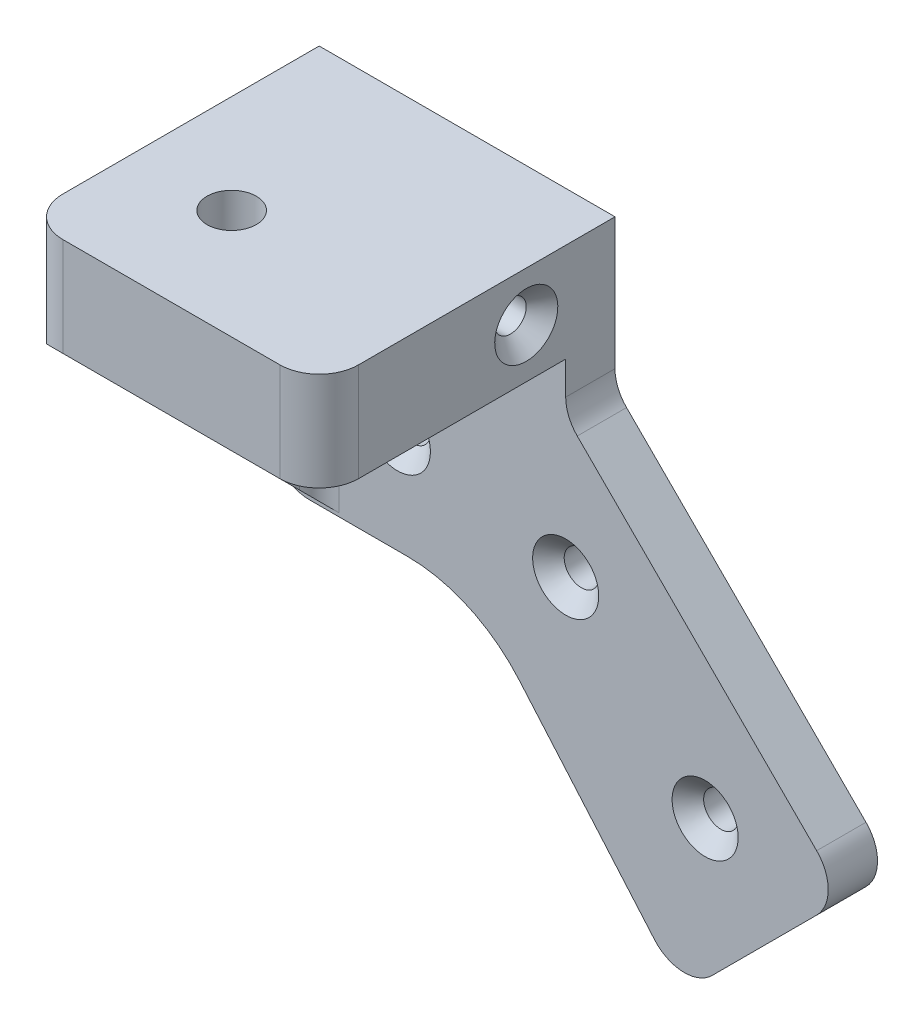
SolidWorks part; units mm, degrees
ref_plane "Front Plane" through (0, 0, 0) normal (0, 0, 1) x (1, 0, 0)
ref_plane "Top Plane" through (0, 0, 0) normal (0, 1, 0) x (1, 0, 0)
ref_plane "Right Plane" through (0, 0, 0) normal (1, 0, 0) x (0, 0, -1)
sketch "Sketch1" plane through (0, 0, 0) normal (0, 0, 1) x (1, 0, 0)
  line L0 (15, 27.5) -> (15, 12.5)
  line L5 (-15, 27.5) -> (15, 27.5)
  line L6 (-15, 27.5) -> (-15, -27.5)
  line L7 (-15, -27.5) -> (15, -27.5)
  line L9 (15, 12.5) -> (43.2843, -15.7843)
  line L10 (-15, -27.5) -> (15, 27.5) construction
  line L11 (43.2843, -15.7843) -> (23.2843, -35.7843)
  line L12 (23.2843, -35.7843) -> (15, -27.5)
  point P0 (0, 0)
  dimension "D1" = 45
  dimension "D2" = 55
  dimension "D3" = 30
  dimension "D4" = 40
  dimension "D5" = 15
extrude "Boss-Extrude1" add sketch "Sketch1" along normal blind 5
sketch "Sketch3" plane through (0, 0, 5) normal (0, 0, 1) x (1, 0, 0)
  line L0 (15, 12.5) -> (15, 27.5) construction
  line L1 (-15, 27.5) -> (15, 27.5)
  line L2 (-15, 27.5) -> (-15, 17.5)
  line L3 (-15, 17.5) -> (15, 17.5)
  line L4 (15, 27.5) -> (15, 17.5)
  dimension "D1" = 10
extrude "Boss-Extrude2" add sketch "Sketch3" along normal blind 25
sketch "Sketch4" plane through (0, 27.5, 0) normal (0, 1, 0) x (1, 0, 0)
  line L0 (-15, -30) -> (-15, 0) construction
  line L1 (15, -30) -> (-15, -30) construction
  line L2 (15, -30) -> (15, -5) construction
  line L3 (15, -5) -> (-15, -5) construction
  line L4 (-15, -30) -> (-15, -5) construction
  line L5 (15, -30) -> (15, 0) construction
  line L6 (-15, 0) -> (15, 0) construction
  line L7 (-15, 0) -> (-15, 5) construction
  line L8 (-15, 5) -> (15, 5) construction
  line L9 (15, 0) -> (15, 5) construction
  circle A0 centre (-5, -18.88) radius 2.5
  circle A1 centre (-5, -18.88) radius 6.5 construction
  dimension "D3" = 13
  dimension "D4" = 5
  dimension "D1" = 25
  dimension "D2" = 5
  dimension "D5" = 23.88
  dimension "D6" = 20
extrude "Cut-Extrude1" cut sketch "Sketch4" against normal through all
sketch "Sketch6" plane through (-15, 0, 0) normal (-1, 0, 0) x (0, 0, 1)
  line L0 (30, 17.5) -> (5, -7.5)
  line L1 (5, 17.5) -> (5, -27.5) construction
  dimension "D1" = 45
rib "Rib1" sketch "Sketch6" sketch "Sketch6" thickness 5 extrusion direction parallel to sketch draft on no parameters "D1"=5
sketch "Sketch7" plane through (0, 0, 5) normal (0, 0, 1) x (1, 0, 0)
  line L0 (10.2934, -13.0651) -> (26.8198, -32.2487)
  line L1 (-15, -7.8553) -> (-1.0711, -7.8553)
  line L2 (-15, -7.8553) -> (-15, -27.5)
  line L3 (-15, -7.5) -> (-15, -27.5) construction
  line L4 (-15, -27.5) -> (15, -27.5) construction
  line L5 (15, 27.5) -> (-15, 27.5) construction
  line L6 (23.2843, -35.7843) -> (43.2843, -15.7843) construction
  line L7 (-15, -27.5) -> (23.2843, -35.7843)
  line L8 (23.2843, -35.7843) -> (26.8198, -32.2487)
  arc A0 (10.2934, -13.0651) -> (-1.0711, -7.8553) centre (-1.0711, -22.8553) ccw
  circle A1 centre (-1.0711, -22.8553) radius 14 construction
  dimension "D1" = 1
  dimension "D2" = 5
extrude "Cut-Extrude2" cut sketch "Sketch7" against normal up to vertex (5 mm away) up to point (-15, -27.5, 0)
sketch "Sketch8" plane through (0, 17.5, 0) normal (0, -1, 0) x (-1, 0, 0)
  line L1 (0.2657, -18.88) -> (2.6329, -22.98)
  line L2 (2.6329, -22.98) -> (7.3671, -22.98)
  line L3 (7.3671, -22.98) -> (9.7343, -18.88)
  line L4 (9.7343, -18.88) -> (7.3671, -14.78)
  line L5 (7.3671, -14.78) -> (2.6329, -14.78)
  line L6 (2.6329, -14.78) -> (0.2657, -18.88)
  circle A0 centre (5, -18.88) radius 4.1 construction
  dimension "D1" = 8.2
extrude "Cut-Extrude3" cut sketch "Sketch8" against normal blind 5
fillet "Fillet1" radius 4 2 edges at (-15, 22.5, 30) (15, 22.5, 30)
sketch "Sketch9" plane through (0, 0, 5) normal (0, 0, 1) x (1, 0, 0)
  line L0 (15, -1.6421) -> (22.0711, 5.4289) construction
  line L1 (43.2843, -15.7843) -> (15, 12.5) construction
  line L2 (29.1421, -15.7843) -> (36.2132, -8.7132) construction
  line L3 (26.8198, -32.2487) -> (43.2843, -15.7843) construction
  line L4 (15, 12.5) -> (-5.3553, -7.8553) construction
  line L5 (-1.0711, -7.8553) -> (-15, -7.8553) construction
  line L6 (15, 12.5) -> (-15, 12.5) construction
  line L7 (-15, 13.5) -> (-15, -7.5) construction
  circle A0 centre (15, -1.6421) radius 1.75
  circle A1 centre (29.1421, -15.7843) radius 1.75
  circle A2 centre (-2.0711, 2.5) radius 1.75
  dimension "D1" = 3.5
  dimension "D5" = 5
  dimension "D2" = 10
  dimension "D3" = 10
  dimension "D4" = 20
  dimension "D6" = 10
extrude "Cut-Extrude4" cut sketch "Sketch9" against normal through all
chamfer "Chamfer1" distance 1.6 angle 45 3 edges at (30.8921, -15.7843, 5) (16.75, -1.6421, 5) (-0.3211, 2.5, 5)
fillet "Fillet2" radius 4 4 edges at (15, 12.5, 2.5) (43.2843, -15.7843, 2.5) (26.8198, -32.2487, 2.5) (-15, -7.8553, 2.5)
sketch "Sketch10" plane through (15, 0, 0) normal (1, 0, 0) x (0, 0, -1)
  line L0 (-9, 17.5) -> (-9, 27.5) construction
  line L1 (-26, 17.5) -> (-5, 17.5) construction
  line L2 (-26, 27.5) -> (0, 27.5) construction
  line L3 (0, 14.1569) -> (0, 27.5) construction
  circle A0 centre (-9, 22.5) radius 1.6
  dimension "D1" = 3.2
  dimension "D2" = 9
extrude "Cut-Extrude5" cut sketch "Sketch10" against normal through all
sketch "Sketch11" plane through (-15, 0, 0) normal (-1, 0, 0) x (0, 0, 1)
  line L1 (10.5877, 19.75) -> (12.1754, 22.5)
  line L2 (12.1754, 22.5) -> (10.5877, 25.25)
  line L3 (10.5877, 25.25) -> (7.4123, 25.25)
  line L4 (7.4123, 25.25) -> (5.8246, 22.5)
  line L5 (5.8246, 22.5) -> (7.4123, 19.75)
  line L6 (7.4123, 19.75) -> (10.5877, 19.75)
  circle A0 centre (9, 22.5) radius 2.75 construction
  dimension "D1" = 5.5
extrude "Cut-Extrude6" cut sketch "Sketch11" against normal blind 4
chamfer "Chamfer2" distance 1.6 angle 45 1 edges at (15, 24.1, 9)
fillet "Fillet3" radius 2 1 edges at (-10, 5, 5)
